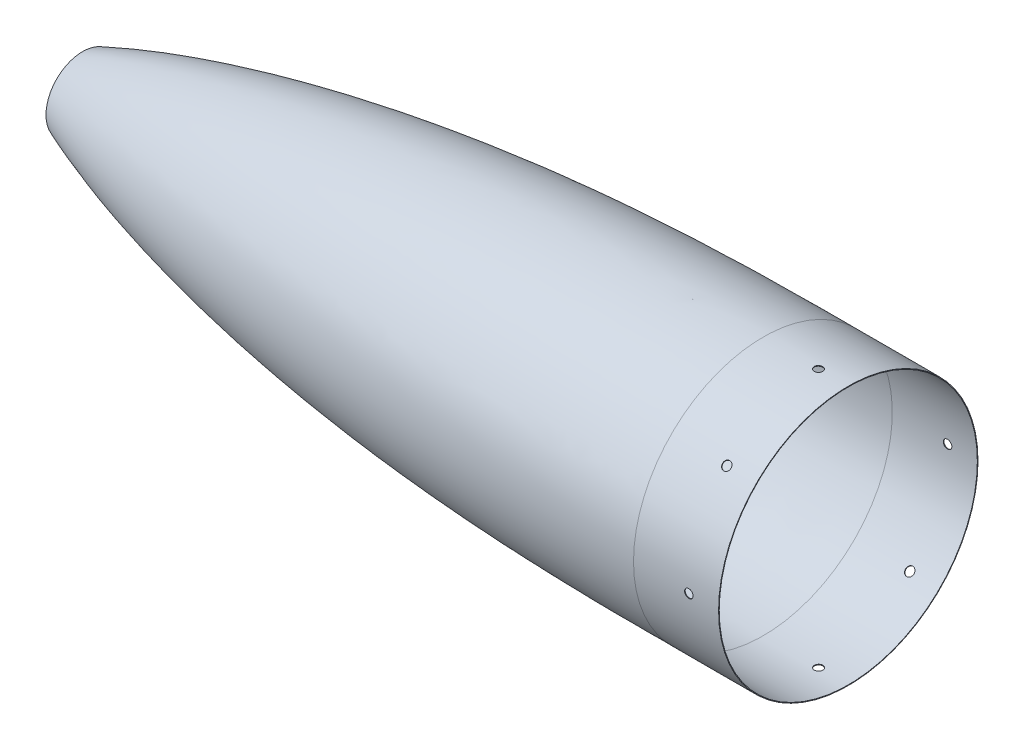
SolidWorks part; units mm, degrees
material "A-Glasfaser"
ref_plane "Ebene vorne" through (0, 0, 0) normal (0, 0, 1) x (1, 0, 0)
ref_plane "Ebene oben" through (0, 0, 0) normal (0, 1, 0) x (1, 0, 0)
ref_plane "Ebene rechts" through (0, 0, 0) normal (1, 0, 0) x (0, 0, -1)
sketch "Skizze2" plane through (0, 0, 0) normal (0, 0, 1) x (1, 0, 0)
  line L0 (0, 0) -> (350.0875, 0)
  line L1 (350.0875, 0) -> (350.0875, 61) construction
  line L2 (350.0875, 0) -> (390.0875, 0)
  line L3 (390.0875, 0) -> (390.0875, 61)
  line L4 (390.0875, 61) -> (350.0875, 61)
  spline S0 degree 4 poles (0, 0) (0.0018, 0.0116) (0.0065, 0.0344) (0.0206, 0.0789) (0.056, 0.1653) (0.1053, 0.2616) (0.1674, 0.3676) (0.2551, 0.5034) (0.3917, 0.6969) (0.6399, 1.0093) (1.0926, 1.5078) (1.8817, 2.2639) (3.2261, 3.3865) (5.4912, 5.0305) (9.1406, 7.3324) (14.9363, 10.5118) (22.9256, 14.3131) (35.1611, 19.4169) (51.255, 25.164) (70.3383, 31.0035) (92.1933, 36.6947) (114.2329, 41.6146) (136.413, 45.8534) (158.7014, 49.476) (181.0744, 52.5302) (203.5129, 55.0555) (226.0014, 57.0857) (248.5267, 58.6531) (271.0775, 59.7904) (293.6445, 60.5347) (316.22, 60.9314) (333.1538, 61.0152) (344.4429, 61.0087) (350.0875, 61) knots 0 0 0 0 0 0.00013 0.000259 0.000518 0.001037 0.001331 0.001625 0.002316 0.003669 0.005764 0.009105 0.014456 0.023127 0.036858 0.057044 0.087908 0.121441 0.184195 0.246949 0.309704 0.372458 0.435212 0.497966 0.56072 0.623475 0.686229 0.748983 0.811737 0.874492 0.937246 1 1 1 1 1 construction
  spline S1 degree 4 poles (0, 0) (0.0018, 0.0116) (0.0065, 0.0344) (0.0206, 0.0789) (0.056, 0.1653) (0.1053, 0.2616) (0.1674, 0.3676) (0.2551, 0.5034) (0.3917, 0.6969) (0.6399, 1.0093) (1.0926, 1.5078) (1.8817, 2.2639) (3.2261, 3.3865) (5.4912, 5.0305) (9.1406, 7.3324) (14.9363, 10.5118) (22.9256, 14.3131) (35.1611, 19.4169) (51.255, 25.164) (70.3383, 31.0035) (92.1933, 36.6947) (114.2329, 41.6146) (136.413, 45.8534) (158.7014, 49.476) (181.0744, 52.5302) (203.5129, 55.0555) (226.0014, 57.0857) (248.5267, 58.6531) (271.0775, 59.7904) (293.6445, 60.5347) (316.22, 60.9314) (333.1538, 61.0152) (344.4429, 61.0087) (350.0875, 61) knots 0 0 0 0 0 0.00013 0.000259 0.000518 0.001037 0.001331 0.001625 0.002316 0.003669 0.005764 0.009105 0.014456 0.023127 0.036858 0.057044 0.087908 0.121441 0.184195 0.246949 0.309704 0.372458 0.435212 0.497966 0.56072 0.623475 0.686229 0.748983 0.811737 0.874492 0.937246 1 1 1 1 1
  dimension "D1" = 61
  dimension "D2" = 40
revolve "Rotation1" add sketch "Skizze2" angle 360 about L0 region at (229.9953, 26.2946, 0)
shell "Schale1" thickness 0.3 removed face at (390.0875, 0, 61)
sketch "Skizze4" plane through (0, 0, 0) normal (1, 0, 0) x (0, 0, -1)
  circle A0 centre (0, 0) radius 60
  dimension "D1" = 120
extrude "Schnitt-Linear austragen2" cut sketch "Skizze4" along normal blind 30
sketch "Skizze5" plane through (0, 0, 0) normal (0, 0, 1) x (1, 0, 0)
  line L0 (390.0875, -60.7) -> (390.0875, 60.7) construction
  circle A0 centre (376.0875, 0) radius 2
  dimension "D1" = 4
  dimension "D2" = 14
extrude "Schnitt-Linear austragen3" cut sketch "Skizze5" along normal through all
pattern_circular "Kreismuster1" count 8 over 360 about axis through (0, 0, 0) along (1, 0, 0) of "Schnitt-Linear austragen3" reverse direction yes
equation "\"L\"= 350'length"
equation "\"C\"= 2 / 3'C-value"
